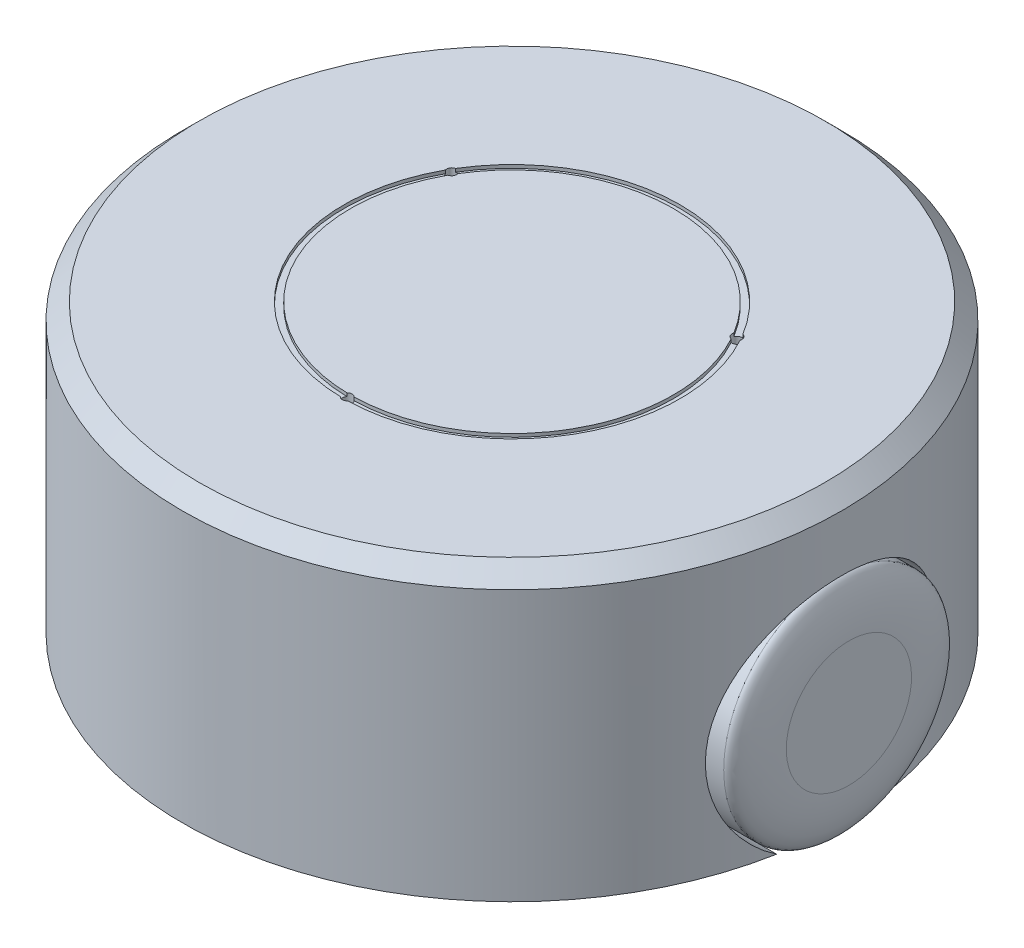
SolidWorks part; units mm, degrees
ref_plane "Alzado" through (0, 0, 0) normal (0, 0, 1) x (1, 0, 0)
ref_plane "Planta" through (0, 0, 0) normal (0, 1, 0) x (1, 0, 0)
ref_plane "Vista lateral" through (0, 0, 0) normal (1, 0, 0) x (0, 0, -1)
sketch "Croquis1" plane through (0, 0, 0) normal (0, 1, 0) x (1, 0, 0)
  circle A0 centre (0, 0) radius 100
  dimension "D1" = 200
extrude "Saliente-Extruir1" add sketch "Croquis1" along normal blind 87
chamfer "Chaflán1" distance 5 angle 45 1 edges at (0, 87, 100)
sketch "Croquis2" plane through (0, 0, 0) normal (1, 0, 0) x (0, 0, -1)
  line L0 (-100, 0) -> (100, 0) construction
  circle A0 centre (0, 30) radius 35
  dimension "D1" = 70
  dimension "D2" = 30
extrude "Cortar-Extruir1" cut sketch "Croquis2" against normal through all both and the other way through all
sketch "Croquis4" plane through (0, 0, 0) normal (0, 1, 0) x (1, 0, 0)
  line L1 (-62.2504, -59.2285) -> (62.2504, -59.2285)
  line L2 (-62.2504, -59.2285) -> (-62.2504, 59.2285)
  line L3 (-62.2504, 59.2285) -> (62.2504, 59.2285)
  line L4 (62.2504, -59.2285) -> (62.2504, 59.2285)
  line L5 (-62.2504, -59.2285) -> (62.2504, 59.2285) construction
  line L6 (-62.2504, 59.2285) -> (62.2504, -59.2285) construction
  point P0 (0, 0)
extrude "Saliente-Extruir2" add sketch "Croquis4" along normal through all
sketch "Croquis5" plane through (-62.2504, 0, 0) normal (-1, 0, 0) x (0, 0, 1)
  circle A0 centre (0, 30) radius 34
  dimension "D1" = 68
extrude "Saliente-Extruir3" add sketch "Croquis5" along normal blind 40
fillet "Redondeo1" radius 4 1 edges at (-102.2504, 30, 34) second distance 15 first distance on face at (-102.2504, 30, 34)
mirror "Simetría2" about plane through (0, 0, 0) normal (1, 0, 0) of "Redondeo1", "Saliente-Extruir3"
sketch "Croquis6" plane through (0, 87, 0) normal (0, 1, 0) x (1, 0, 0)
  circle A0 centre (0, 0) radius 51
  circle A1 centre (0, 0) radius 49
  dimension "D1" = 98
  dimension "D2" = 102
extrude "Cortar-Extruir2" cut sketch "Croquis6" against normal blind 1 and the other way through all
sketch "Croquis7" plane through (0, 87, 0) normal (0, 1, 0) x (1, 0, 0)
  line L0 (0, 0) -> (0, -50) construction
  line L1 (0, 0) -> (-43.3013, 25) construction
  line L2 (0, 0) -> (43.3013, 25) construction
  circle A0 centre (0, -50) radius 1.5
  circle A1 centre (-43.3013, 25) radius 1.5
  circle A2 centre (43.3013, 25) radius 1.5
  point P10 (0, 0)
  dimension "D1" = 3
  dimension "D3" = 50
  dimension "D2" = 3
extrude "Cortar-Extruir3" cut sketch "Croquis7" against normal blind 10
